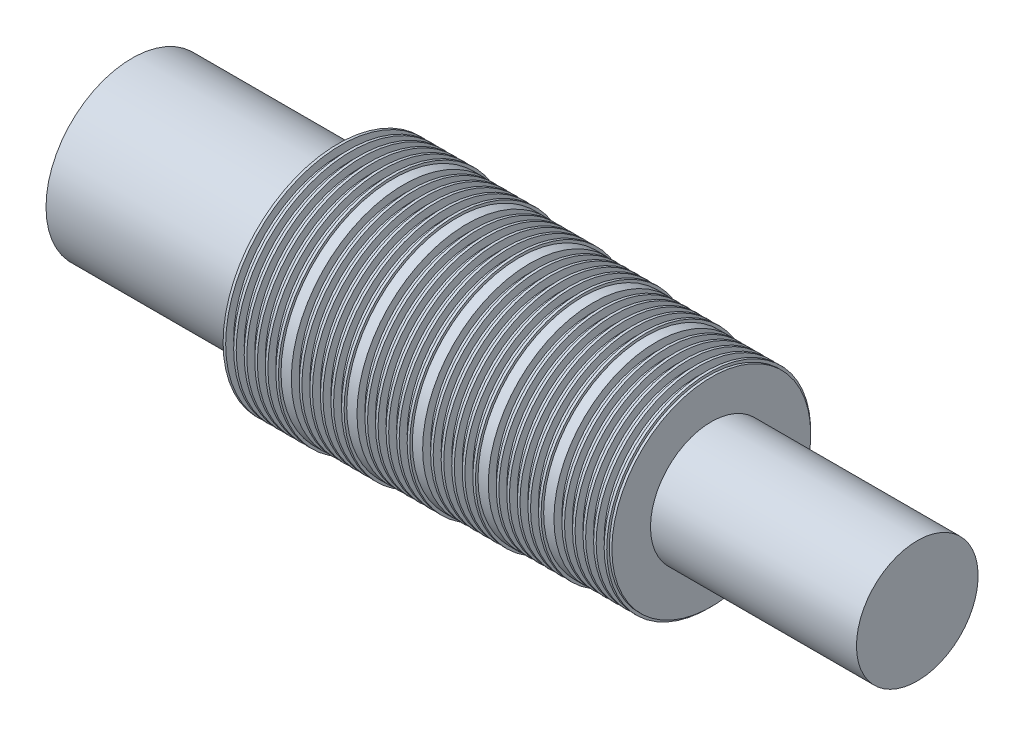
SolidWorks part; units mm, degrees
ref_plane "Front Plane" through (0, 0, 0) normal (0, 0, 1) x (1, 0, 0)
ref_plane "Top Plane" through (0, 0, 0) normal (0, 1, 0) x (1, 0, 0)
ref_plane "Right Plane" through (0, 0, 0) normal (1, 0, 0) x (0, 0, -1)
sketch "Sketch1" plane through (0, 0, 0) normal (0, 0, 1) x (1, 0, 0)
  line L24 (20.574, 11.334) -> (20.574, 10.5466)
  line L25 (20.574, 10.5466) -> (21.3614, 10.5466)
  line L26 (21.3614, 10.5466) -> (21.3614, 11.334)
  line L27 (21.3614, 11.334) -> (21.6154, 11.334)
  line L28 (21.6154, 11.334) -> (21.6154, 10.5466)
  line L29 (21.6154, 10.5466) -> (22.4028, 10.5466)
  line L30 (22.4028, 10.5466) -> (22.4028, 11.334)
  line L31 (22.4028, 11.334) -> (22.6568, 11.334)
  line L32 (22.6568, 11.334) -> (22.6568, 10.5466)
  line L33 (22.6568, 10.5466) -> (23.4442, 10.5466)
  line L34 (23.4442, 10.5466) -> (23.4442, 11.334)
  line L35 (23.4442, 11.334) -> (23.6982, 11.334)
  line L36 (23.6982, 11.334) -> (23.6982, 10.5466)
  line L37 (23.6982, 10.5466) -> (24.4856, 10.5466)
  line L38 (24.4856, 10.5466) -> (24.4856, 11.334)
  line L39 (24.4856, 11.334) -> (24.7396, 11.334)
  line L40 (24.7396, 11.334) -> (24.7396, 10.5466)
  line L41 (24.7396, 10.5466) -> (25.527, 10.5466)
  line L42 (25.527, 10.5466) -> (25.527, 11.334)
  line L43 (25.527, 11.334) -> (25.781, 11.334)
  line L44 (25.781, 11.334) -> (25.781, 11.08)
  line L45 (25.781, 11.08) -> (26.797, 11.08)
  line L46 (26.797, 11.08) -> (26.797, 10.2926)
  line L47 (26.797, 10.2926) -> (27.5844, 10.2926)
  line L48 (27.5844, 10.2926) -> (27.5844, 11.08)
  line L49 (27.5844, 11.08) -> (27.8384, 11.08)
  line L50 (27.8384, 11.08) -> (27.8384, 10.2926)
  line L51 (27.8384, 10.2926) -> (28.6258, 10.2926)
  line L52 (28.6258, 10.2926) -> (28.6258, 11.08)
  line L53 (28.6258, 11.08) -> (28.8798, 11.08)
  line L54 (28.8798, 11.08) -> (28.8798, 10.2926)
  line L55 (28.8798, 10.2926) -> (29.6672, 10.2926)
  line L56 (29.6672, 10.2926) -> (29.6672, 11.08)
  line L57 (29.6672, 11.08) -> (29.9212, 11.08)
  line L58 (29.9212, 11.08) -> (29.9212, 10.2926)
  line L59 (29.9212, 10.2926) -> (30.7086, 10.2926)
  line L60 (30.7086, 10.2926) -> (30.7086, 11.08)
  line L61 (30.7086, 11.08) -> (30.9626, 11.08)
  line L62 (30.9626, 11.08) -> (30.9626, 10.2926)
  line L63 (30.9626, 10.2926) -> (31.75, 10.2926)
  line L64 (31.75, 10.2926) -> (31.75, 11.08)
  line L65 (31.75, 11.08) -> (32.004, 11.08)
  line L66 (32.004, 11.08) -> (32.004, 10.826)
  line L67 (32.004, 10.826) -> (33.02, 10.826)
  line L68 (33.02, 10.826) -> (33.02, 10.0386)
  line L69 (33.02, 10.0386) -> (33.8074, 10.0386)
  line L70 (33.8074, 10.0386) -> (33.8074, 10.826)
  line L71 (33.8074, 10.826) -> (34.0614, 10.826)
  line L72 (34.0614, 10.826) -> (34.0614, 10.0386)
  line L73 (34.0614, 10.0386) -> (34.8488, 10.0386)
  line L74 (34.8488, 10.0386) -> (34.8488, 10.826)
  line L75 (34.8488, 10.826) -> (35.1028, 10.826)
  line L76 (35.1028, 10.826) -> (35.1028, 10.0386)
  line L77 (35.1028, 10.0386) -> (35.8902, 10.0386)
  line L78 (35.8902, 10.0386) -> (35.8902, 10.826)
  line L79 (35.8902, 10.826) -> (36.1442, 10.826)
  line L80 (36.1442, 10.826) -> (36.1442, 10.0386)
  line L81 (36.1442, 10.0386) -> (36.9316, 10.0386)
  line L82 (36.9316, 10.0386) -> (36.9316, 10.826)
  line L83 (36.9316, 10.826) -> (37.1856, 10.826)
  line L84 (37.1856, 10.826) -> (37.1856, 10.0386)
  line L85 (37.1856, 10.0386) -> (37.973, 10.0386)
  line L86 (37.973, 10.0386) -> (37.973, 10.826)
  line L87 (37.973, 10.826) -> (38.227, 10.826)
  line L88 (38.227, 10.826) -> (38.227, 10.572)
  line L89 (38.227, 10.572) -> (39.243, 10.572)
  line L90 (39.243, 10.572) -> (39.243, 9.7846)
  line L91 (39.243, 9.7846) -> (40.0304, 9.7846)
  line L92 (40.0304, 9.7846) -> (40.0304, 10.572)
  line L93 (40.0304, 10.572) -> (40.2844, 10.572)
  line L94 (40.2844, 10.572) -> (40.2844, 9.7846)
  line L95 (40.2844, 9.7846) -> (41.0718, 9.7846)
  line L96 (41.0718, 9.7846) -> (41.0718, 10.572)
  line L97 (41.0718, 10.572) -> (41.3258, 10.572)
  line L98 (41.3258, 10.572) -> (41.3258, 9.7846)
  line L99 (41.3258, 9.7846) -> (42.1132, 9.7846)
  line L100 (42.1132, 9.7846) -> (42.1132, 10.572)
  line L101 (42.1132, 10.572) -> (42.3672, 10.572)
  line L102 (42.3672, 10.572) -> (42.3672, 9.7846)
  line L103 (42.3672, 9.7846) -> (43.1546, 9.7846)
  line L104 (43.1546, 9.7846) -> (43.1546, 10.572)
  line L105 (43.1546, 10.572) -> (43.4086, 10.572)
  line L106 (43.4086, 10.572) -> (43.4086, 9.7846)
  line L107 (43.4086, 9.7846) -> (44.196, 9.7846)
  line L108 (44.196, 9.7846) -> (44.196, 10.572)
  line L109 (44.196, 10.572) -> (44.45, 10.572)
  line L110 (44.45, 10.572) -> (44.45, 10.318)
  line L111 (44.45, 10.318) -> (45.466, 10.318)
  line L112 (45.466, 10.318) -> (45.466, 9.5306)
  line L113 (45.466, 9.5306) -> (46.2534, 9.5306)
  line L114 (46.2534, 9.5306) -> (46.2534, 10.318)
  line L115 (46.2534, 10.318) -> (46.5074, 10.318)
  line L116 (46.5074, 10.318) -> (46.5074, 9.5306)
  line L117 (46.5074, 9.5306) -> (47.2948, 9.5306)
  line L118 (47.2948, 9.5306) -> (47.2948, 10.318)
  line L119 (47.2948, 10.318) -> (47.5488, 10.318)
  line L120 (47.5488, 10.318) -> (47.5488, 9.5306)
  line L121 (47.5488, 9.5306) -> (48.3362, 9.5306)
  line L122 (48.3362, 9.5306) -> (48.3362, 10.318)
  line L123 (48.3362, 10.318) -> (48.5902, 10.318)
  line L124 (48.5902, 10.318) -> (48.5902, 9.5306)
  line L125 (48.5902, 9.5306) -> (49.3776, 9.5306)
  line L126 (49.3776, 9.5306) -> (49.3776, 10.318)
  line L127 (49.3776, 10.318) -> (49.6316, 10.318)
  line L128 (49.6316, 10.318) -> (49.6316, 9.5306)
  line L129 (49.6316, 9.5306) -> (50.419, 9.5306)
  line L130 (50.419, 9.5306) -> (50.419, 10.318)
  line L131 (50.419, 10.318) -> (50.673, 10.318)
  line L132 (50.673, 10.318) -> (50.673, 10.064)
  line L133 (50.673, 10.064) -> (51.689, 10.064)
  line L134 (51.689, 10.064) -> (51.689, 9.2766)
  line L135 (51.689, 9.2766) -> (52.4764, 9.2766)
  line L136 (52.4764, 9.2766) -> (52.4764, 10.064)
  line L137 (52.4764, 10.064) -> (52.7304, 10.064)
  line L138 (52.7304, 10.064) -> (52.7304, 9.2766)
  line L139 (52.7304, 9.2766) -> (53.5178, 9.2766)
  line L140 (53.5178, 9.2766) -> (53.5178, 10.064)
  line L141 (53.5178, 10.064) -> (53.7718, 10.064)
  line L142 (53.7718, 10.064) -> (53.7718, 9.2766)
  line L143 (53.7718, 9.2766) -> (54.5592, 9.2766)
  line L144 (54.5592, 9.2766) -> (54.5592, 10.064)
  line L145 (54.5592, 10.064) -> (54.8132, 10.064)
  line L146 (54.8132, 10.064) -> (54.8132, 9.2766)
  line L147 (54.8132, 9.2766) -> (55.6006, 9.2766)
  line L148 (55.6006, 9.2766) -> (55.6006, 10.064)
  line L149 (55.6006, 10.064) -> (55.8546, 10.064)
  line L150 (55.8546, 10.064) -> (55.8546, 9.2766)
  line L151 (55.8546, 9.2766) -> (56.642, 9.2766)
  line L152 (56.642, 9.2766) -> (56.642, 10.064)
  line L153 (56.642, 10.064) -> (56.896, 10.064)
  line L154 (56.896, 10.064) -> (56.896, 9.81)
  line L155 (56.896, 9.81) -> (57.15, 9.81)
  line L156 (20.32, 8.4836) -> (0, 8.4836)
  line L157 (0, 8.4836) -> (0, 0)
  line L158 (0, 0) -> (61.976, 0)
  line L159 (57.15, 6) -> (57.15, 9.81)
  line L160 (20.574, 11.334) -> (20.32, 11.334)
  line L161 (20.32, 11.334) -> (20.32, 8.4836)
  line L162 (57.15, 6) -> (77.47, 6)
  line L163 (77.47, 6) -> (77.47, 0)
  line L164 (77.47, 0) -> (61.976, 0)
  point P5 (57.023, 9.81)
  point P6 (67.31, 6)
  dimension "D1" = 8.4836
  dimension "D8" = 0.254
  dimension "D9" = 20.32
  dimension "D3" = 0.254
  dimension "D4" = 0.7874
  dimension "D5" = 0.7874
  dimension "D6" = 0.254
  dimension "D7" = 1.016
  dimension "D2" = 9.81
  dimension "D10" = 6
  dimension "D11" = 20.32
revolve "Revolve1" add sketch "Sketch1" angle 360 about L158
equation "\"kero_radius\"=0.334in"
equation "\"D1@Sketch1\"=\"kero_radius\""
equation "\"lox_radius\"=0.23622in"
equation "\"Cavity_width\"=0.031in"
equation "\"tooth_width\"=0.01in"
equation "\"cavity_depth\"=0.031in"
equation "\"seal_step\"=0.01in"
equation "\"purge_length\"=0.04in"
equation "\"D3@Sketch1\"=\"tooth_width\""
equation "\"D4@Sketch1\"=\"Cavity_width\""
equation "\"D5@Sketch1\"=\"cavity_depth\""
equation "\"D6@Sketch1\"=\"seal_step\""
equation "\"D7@Sketch1\"=\"purge_length\""
equation "\"D2@Sketch1\"=\"lox_radius\"+.15"
equation "\"D10@Sketch1\"=\"lox_radius\""
